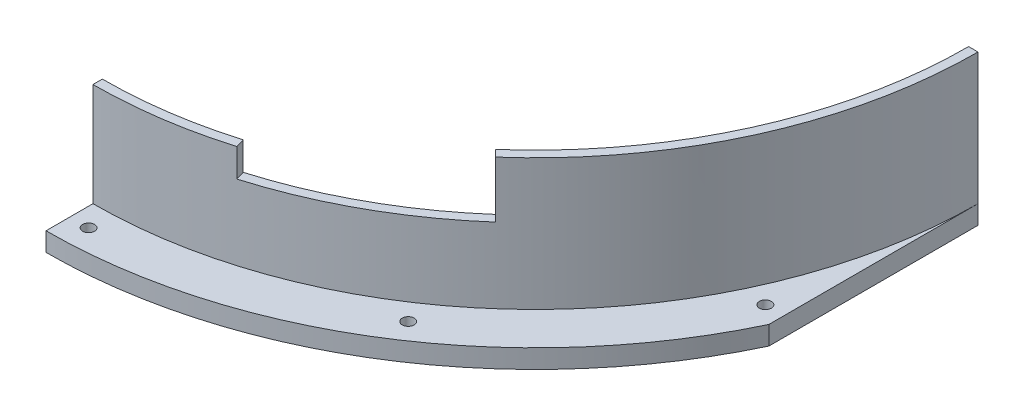
SolidWorks part; units mm, degrees
material "PET"
ref_plane "Front" through (0, 0, 0) normal (0, 0, 1) x (1, 0, 0)
ref_plane "Top" through (0, 0, 0) normal (0, 1, 0) x (1, 0, 0)
ref_plane "Right" through (0, 0, 0) normal (1, 0, 0) x (0, 0, -1)
sketch "Sketch1" plane through (0, 0, 0) normal (0, 1, 0) x (1, 0, 0)
  line L0 (165.608, 0) -> (146.558, 0)
  line L1 (0, -165.608) -> (0, -146.558)
  arc A0 (0, -165.608) -> (165.608, 0) centre (0, 0) ccw
  arc A1 (0, -146.558) -> (146.558, 0) centre (0, 0) ccw
  dimension "D1" = 146.558
  dimension "D2" = 19.05
extrude "Boss-Extrude1" add sketch "Sketch1" along normal blind 6.35
sketch "Sketch2" plane through (0, 6.35, 0) normal (0, 1, 0) x (1, 0, 0)
  line L0 (165.608, 0) -> (146.558, 0) construction
  line L2 (146.558, 0) -> (149.733, 0)
  line L3 (0, -146.558) -> (0, -149.733)
  arc A0 (0, -146.558) -> (146.558, 0) centre (0, 0) ccw
  arc A1 (0, -149.733) -> (149.733, 0) centre (0, 0) ccw
  dimension "D1" = 3.175
extrude "Boss-Extrude2" add sketch "Sketch2" along normal blind 44.45
sketch "Sketch3" plane through (0, 50.8, 0) normal (0, 1, 0) x (1, 0, 0)
  line L0 (96.6779, -110.1483) -> (98.9276, -112.398)
  line L1 (0, -146.558) -> (0, -149.733)
  line L2 (103.6322, -103.6322) -> (105.8772, -105.8772) construction
  arc A0 (0, -146.558) -> (146.558, 0) centre (0, 0) ccw construction
  arc A1 (0, -149.733) -> (149.733, 0) centre (0, 0) ccw construction
  arc A2 (98.9276, -112.398) -> (0, -149.733) centre (0, 0) cw
  arc A3 (0, -146.558) -> (96.6779, -110.1483) centre (0, 0) ccw
  arc A4 (0, -149.733) -> (149.733, 0) centre (0, 0) ccw construction
  dimension "D1" = 9.525
extrude "Cut-Extrude1" cut sketch "Sketch3" against normal blind 9.525
sketch "Sketch4" plane through (0, 41.275, 0) normal (0, 1, 0) x (1, 0, 0)
  line L0 (96.6779, -110.1483) -> (98.9276, -112.398)
  line L1 (98.9276, -112.398) -> (96.6779, -110.1483) construction
  line L2 (41.6294, -140.5213) -> (42.5313, -143.5655)
  line L4 (51.6534, -137.1538) -> (52.8691, -140.0886) construction
  arc A0 (0, -146.558) -> (96.6779, -110.1483) centre (0, 0) ccw construction
  arc A2 (98.9276, -112.398) -> (42.5313, -143.5655) centre (0, 0) cw
  arc A3 (0, -149.733) -> (98.9276, -112.398) centre (0, 0) ccw construction
  arc A4 (96.6779, -110.1483) -> (41.6294, -140.5213) centre (0, 0) cw
  dimension "D1" = 6
extrude "Cut-Extrude2" cut sketch "Sketch4" against normal blind 9.525
sketch "Sketch5" plane through (0, 6.35, 0) normal (0, 1, 0) x (1, 0, 0)
  line L1 (149.733, 0) -> (165.608, 0)
  line L2 (149.733, 0) -> (149.733, -76.2)
  line L3 (149.733, -76.2) -> (165.608, -76.2)
  line L4 (165.608, 0) -> (165.608, -76.2)
  dimension "D1" = 76.2
extrude "Cut-Extrude3" cut sketch "Sketch5" against normal through all
sketch "Sketch8" plane through (0, 6.35, 0) normal (0, 1, 0) x (1, 0, 0)
  line L0 (0, -149.733) -> (0, -165.608) construction
  line L1 (6.35, -157.5426) -> (87.8583, -130.9233) construction
  line L2 (87.8583, -130.9233) -> (143.383, -65.5843) construction
  line L4 (149.733, 0) -> (149.733, -70.7534) construction
  circle A0 centre (0, 0) radius 157.6705 construction
  point P0 (6.35, -157.5426)
  point P2 (87.8583, -130.9233)
  point P4 (143.383, -65.5843)
  point P13 (0, -157.6705)
  dimension "D1" = 6.35
  dimension "D2" = 6.35
hole_wizard "#10-32 Tapped Hole1" positions "Sketch8" profile "Sketch7" tap size "#10-32" standard "ANSI Inch" end condition up to next
sketch "Sketch7" plane through (6.35, 6.35, 157.5426) normal (1, 0, 0) x (0, 0, 1)
  line L0 (0, 0) -> (0, 6.35)
  line L1 (0, 6.35) -> (2.0193, 6.35)
  line L2 (2.0193, 6.35) -> (2.0193, 0)
  line L5 (2.0193, 0) -> (0, 0)
  line L11 (0, -6.35) -> (0, 107.95) construction
  dimension "Thru Tap Drill Dia." = 4.0386
  dimension "Thru Tap Drill Depth" = 6.35
cosmetic thread "Hole Thread1" parameters "D2"=4.826
cosmetic thread "Hole Thread2" parameters "D2"=4.826
cosmetic thread "Hole Thread3" parameters "D2"=4.826
